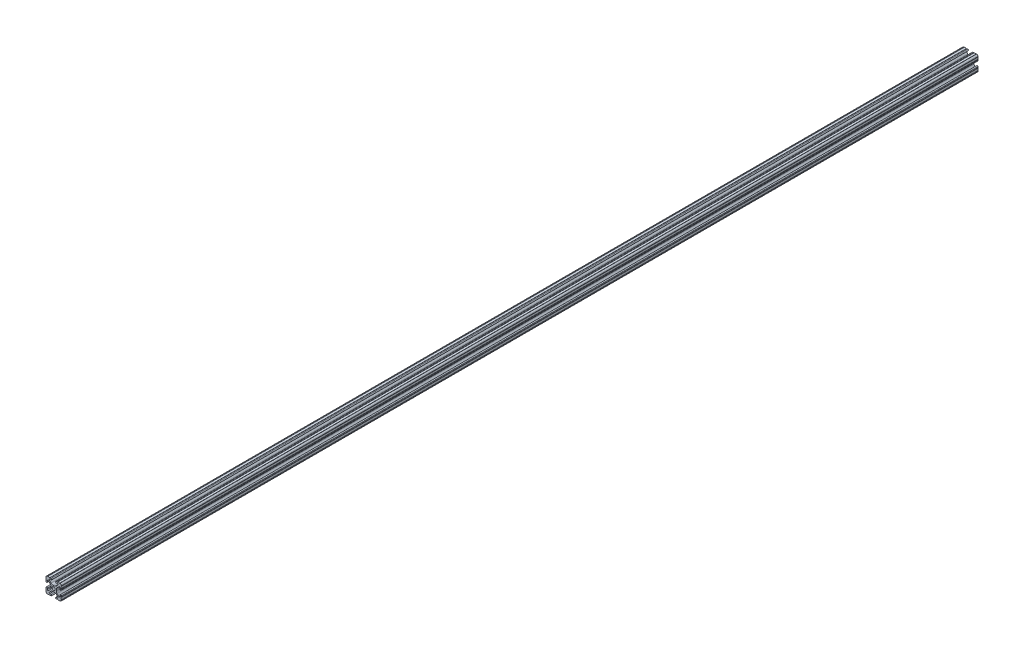
SolidWorks part; units mm, degrees
ref_plane "Front Plane" through (0, 0, 0) normal (0, 0, 1) x (1, 0, 0)
ref_plane "Top Plane" through (0, 0, 0) normal (0, 1, 0) x (1, 0, 0)
ref_plane "Right Plane" through (0, 0, 0) normal (1, 0, 0) x (0, 0, -1)
sketch "Sketch1" plane through (0, 0, 0) normal (0, 0, 1) x (1, 0, 0)
  line L0 (0, 12.7) -> (-12.7814, 12.7) construction
  line L1 (-4.5085, 0) -> (-4.5085, 2.9459)
  line L2 (-6.0437, 12.5461) -> (-10.0976, 12.6876) construction
  line L3 (-11.5616, 12.4229) -> (-4.3159, 12.1699) construction
  line L4 (-6.4364, 10.3486) -> (-6.3592, 12.5571) construction
  line L6 (-2.9459, 4.5085) -> (0, 4.5085)
  line L7 (0, 0) -> (0, 12.7) construction
  line L8 (0, 0) -> (-12.7814, 0) construction
  line L9 (0.7813, 0.7813) -> (-0.7813, -0.7813) construction
  line L10 (-2.9459, 4.5085) -> (-7.1484, 8.711)
  line L11 (-4.5085, 2.9459) -> (-8.711, 7.1484)
  line L13 (0, 0) -> (-12.7814, 12.7814) construction
  line L14 (-10.4131, 12.6987) -> (-4.3048, 12.4853)
  line L15 (-4.3048, 12.4853) -> (-4.382, 10.2769) construction
  line L16 (-4.382, 10.2769) -> (-6.4364, 10.3486)
  line L17 (-12.6987, 10.4131) -> (-12.4853, 4.3048)
  line L18 (-10.2769, 4.382) -> (-10.3486, 6.4364)
  circle A0 centre (0, 0) radius 2.6035
  arc A1 (-4.382, 10.2769) -> (-4.3048, 12.4853) centre (-4.3434, 11.3811) ccw
  arc A2 (-7.1484, 8.711) -> (-6.4364, 10.3486) centre (-6.4698, 9.3896) cw
  arc A3 (-8.711, 7.1484) -> (-10.3486, 6.4364) centre (-9.3896, 6.4698) ccw
  arc A4 (-10.2769, 4.382) -> (-12.4853, 4.3048) centre (-11.3811, 4.3434) cw
  arc A5 (-10.4131, 12.6987) -> (-12.6987, 10.4131) centre (-10.4902, 10.4902) ccw
  arc A6 (-10.4131, 12.6987) -> (-9.7821, 12.6766) centre (-10.0976, 12.6876) ccw
  arc A7 (-6.3592, 12.5571) -> (-5.7282, 12.5351) centre (-6.0437, 12.5461) ccw
  arc A8 (-12.5571, 6.3592) -> (-12.5351, 5.7282) centre (-12.5461, 6.0437) cw
  arc A9 (-12.6987, 10.4131) -> (-12.6766, 9.7821) centre (-12.6876, 10.0976) cw
  dimension "D1" = 5.207
  dimension "D5" = 14.859
  dimension "D9" = 2
  dimension "D2" = 25.4
  dimension "D12" = 0.6314
  dimension "D10" = 2.2098
  dimension "D3" = 9.017
  dimension "D4" = 9.017
  dimension "D6" = 25.4
  dimension "D7" = 6.477
  dimension "D8" = 2.2098
  dimension "D11" = 12.7
sketch "Sketch3" plane through (0, 0, 0) normal (0, 0, 1) x (1, 0, 0)
  line L0 (-2.9459, 4.5085) -> (0, 4.5085) construction
  line L1 (-2.9459, 4.5085) -> (-7.1484, 8.711) construction
  line L2 (-4.382, 10.2769) -> (-6.4364, 10.3486) construction
  line L3 (-10.4131, 12.6987) -> (-4.3048, 12.4853) construction
  line L4 (-4.5085, 0) -> (-4.5085, 2.9459) construction
  line L5 (-4.5085, 2.9459) -> (-8.711, 7.1484) construction
  line L6 (-10.2769, 4.382) -> (-10.3486, 6.4364) construction
  line L7 (-12.6987, 10.4131) -> (-12.4853, 4.3048) construction
  line L8 (-1.1153, 4.5085) -> (1.1153, 4.5085)
  line L9 (-4.2404, 5.803) -> (-7.1484, 8.711)
  line L10 (-4.382, 10.2769) -> (-6.4364, 10.3486)
  line L11 (-9.7821, 12.6766) -> (-6.3592, 12.5571)
  line L12 (-4.5085, -1.1153) -> (-4.5085, 1.1153)
  line L13 (-5.803, 4.2404) -> (-8.711, 7.1484)
  line L14 (-10.2769, 4.382) -> (-10.3486, 6.4364)
  line L15 (-12.6766, 9.7821) -> (-12.5571, 6.3592)
  line L16 (-5.7282, 12.5351) -> (-4.3048, 12.4853)
  line L17 (-12.5351, 5.7282) -> (-12.4853, 4.3048)
  line L18 (0, 0) -> (0, 12.7) construction
  line L19 (0, 0) -> (-12.7814, 0) construction
  line L20 (12.5351, 5.7282) -> (12.4853, 4.3048)
  line L21 (5.7282, 12.5351) -> (4.3048, 12.4853)
  line L22 (12.6766, 9.7821) -> (12.5571, 6.3592)
  line L23 (10.2769, 4.382) -> (10.3486, 6.4364)
  line L24 (5.803, 4.2404) -> (8.711, 7.1484)
  line L25 (4.5085, -1.1153) -> (4.5085, 1.1153)
  line L26 (9.7821, 12.6766) -> (6.3592, 12.5571)
  line L27 (4.382, 10.2769) -> (6.4364, 10.3486)
  line L28 (4.2404, 5.803) -> (7.1484, 8.711)
  line L29 (4.2404, -5.803) -> (7.1484, -8.711)
  line L30 (4.382, -10.2769) -> (6.4364, -10.3486)
  line L31 (9.7821, -12.6766) -> (6.3592, -12.5571)
  line L32 (5.803, -4.2404) -> (8.711, -7.1484)
  line L33 (10.2769, -4.382) -> (10.3486, -6.4364)
  line L34 (12.6766, -9.7821) -> (12.5571, -6.3592)
  line L35 (5.7282, -12.5351) -> (4.3048, -12.4853)
  line L36 (12.5351, -5.7282) -> (12.4853, -4.3048)
  line L37 (-12.5351, -5.7282) -> (-12.4853, -4.3048)
  line L38 (-5.7282, -12.5351) -> (-4.3048, -12.4853)
  line L39 (-12.6766, -9.7821) -> (-12.5571, -6.3592)
  line L40 (-10.2769, -4.382) -> (-10.3486, -6.4364)
  line L41 (-5.803, -4.2404) -> (-8.711, -7.1484)
  line L42 (-9.7821, -12.6766) -> (-6.3592, -12.5571)
  line L43 (-4.382, -10.2769) -> (-6.4364, -10.3486)
  line L44 (-4.2404, -5.803) -> (-7.1484, -8.711)
  line L45 (-1.1153, -4.5085) -> (1.1153, -4.5085)
  arc A0 (-10.4131, 12.6987) -> (-9.7821, 12.6766) centre (-10.0976, 12.6876) ccw construction
  arc A1 (-6.4364, 10.3486) -> (-7.1484, 8.711) centre (-6.4698, 9.3896) ccw construction
  arc A2 (-4.382, 10.2769) -> (-4.3048, 12.4853) centre (-4.3434, 11.3811) ccw construction
  arc A3 (-8.711, 7.1484) -> (-10.3486, 6.4364) centre (-9.3896, 6.4698) ccw construction
  arc A4 (-12.4853, 4.3048) -> (-10.2769, 4.382) centre (-11.3811, 4.3434) ccw construction
  arc A5 (-6.3592, 12.5571) -> (-5.7282, 12.5351) centre (-6.0437, 12.5461) ccw construction
  arc A6 (-10.4131, 12.6987) -> (-12.6987, 10.4131) centre (-10.4902, 10.4902) ccw construction
  arc A7 (-12.6766, 9.7821) -> (-12.6987, 10.4131) centre (-12.6876, 10.0976) ccw construction
  arc A8 (-12.5351, 5.7282) -> (-12.5571, 6.3592) centre (-12.5461, 6.0437) ccw construction
  arc A9 (-10.4131, 12.6987) -> (-9.7821, 12.6766) centre (-10.0976, 12.6876) ccw
  arc A10 (-6.4364, 10.3486) -> (-7.1484, 8.711) centre (-6.4698, 9.3896) ccw
  arc A11 (-4.382, 10.2769) -> (-4.3048, 12.4853) centre (-4.3434, 11.3811) ccw
  arc A12 (-8.711, 7.1484) -> (-10.3486, 6.4364) centre (-9.3896, 6.4698) ccw
  arc A13 (-12.4853, 4.3048) -> (-10.2769, 4.382) centre (-11.3811, 4.3434) ccw
  arc A14 (-6.3592, 12.5571) -> (-5.7282, 12.5351) centre (-6.0437, 12.5461) ccw
  arc A15 (-10.4131, 12.6987) -> (-12.6987, 10.4131) centre (-10.4902, 10.4902) ccw
  arc A16 (-12.6766, 9.7821) -> (-12.6987, 10.4131) centre (-12.6876, 10.0976) ccw
  arc A17 (-12.5351, 5.7282) -> (-12.5571, 6.3592) centre (-12.5461, 6.0437) ccw
  arc A18 (-1.1153, 4.5085) -> (-4.2404, 5.803) centre (-1.1153, 8.9281) cw
  arc A19 (4.5085, 1.1153) -> (5.803, 4.2404) centre (8.9281, 1.1153) cw
  arc A20 (1.1153, 4.5085) -> (4.2404, 5.803) centre (1.1153, 8.9281) ccw
  arc A21 (-4.5085, 1.1153) -> (-5.803, 4.2404) centre (-8.9281, 1.1153) ccw
  arc A22 (12.5351, 5.7282) -> (12.5571, 6.3592) centre (12.5461, 6.0437) cw
  arc A23 (12.6766, 9.7821) -> (12.6987, 10.4131) centre (12.6876, 10.0976) cw
  arc A24 (10.4131, 12.6987) -> (12.6987, 10.4131) centre (10.4902, 10.4902) cw
  arc A25 (6.3592, 12.5571) -> (5.7282, 12.5351) centre (6.0437, 12.5461) cw
  arc A26 (12.4853, 4.3048) -> (10.2769, 4.382) centre (11.3811, 4.3434) cw
  arc A27 (8.711, 7.1484) -> (10.3486, 6.4364) centre (9.3896, 6.4698) cw
  arc A28 (4.382, 10.2769) -> (4.3048, 12.4853) centre (4.3434, 11.3811) cw
  arc A29 (6.4364, 10.3486) -> (7.1484, 8.711) centre (6.4698, 9.3896) cw
  arc A30 (10.4131, 12.6987) -> (9.7821, 12.6766) centre (10.0976, 12.6876) cw
  arc A31 (10.4131, -12.6987) -> (9.7821, -12.6766) centre (10.0976, -12.6876) ccw
  arc A32 (6.4364, -10.3486) -> (7.1484, -8.711) centre (6.4698, -9.3896) ccw
  arc A33 (4.382, -10.2769) -> (4.3048, -12.4853) centre (4.3434, -11.3811) ccw
  arc A34 (8.711, -7.1484) -> (10.3486, -6.4364) centre (9.3896, -6.4698) ccw
  arc A35 (12.4853, -4.3048) -> (10.2769, -4.382) centre (11.3811, -4.3434) ccw
  arc A36 (6.3592, -12.5571) -> (5.7282, -12.5351) centre (6.0437, -12.5461) ccw
  arc A37 (10.4131, -12.6987) -> (12.6987, -10.4131) centre (10.4902, -10.4902) ccw
  arc A38 (12.6766, -9.7821) -> (12.6987, -10.4131) centre (12.6876, -10.0976) ccw
  arc A39 (12.5351, -5.7282) -> (12.5571, -6.3592) centre (12.5461, -6.0437) ccw
  arc A40 (-4.5085, -1.1153) -> (-5.803, -4.2404) centre (-8.9281, -1.1153) cw
  arc A41 (1.1153, -4.5085) -> (4.2404, -5.803) centre (1.1153, -8.9281) cw
  arc A42 (4.5085, -1.1153) -> (5.803, -4.2404) centre (8.9281, -1.1153) ccw
  arc A43 (-1.1153, -4.5085) -> (-4.2404, -5.803) centre (-1.1153, -8.9281) ccw
  arc A44 (-12.5351, -5.7282) -> (-12.5571, -6.3592) centre (-12.5461, -6.0437) cw
  arc A45 (-12.6766, -9.7821) -> (-12.6987, -10.4131) centre (-12.6876, -10.0976) cw
  arc A46 (-10.4131, -12.6987) -> (-12.6987, -10.4131) centre (-10.4902, -10.4902) cw
  arc A47 (-6.3592, -12.5571) -> (-5.7282, -12.5351) centre (-6.0437, -12.5461) cw
  arc A48 (-12.4853, -4.3048) -> (-10.2769, -4.382) centre (-11.3811, -4.3434) cw
  arc A49 (-8.711, -7.1484) -> (-10.3486, -6.4364) centre (-9.3896, -6.4698) cw
  arc A50 (-4.382, -10.2769) -> (-4.3048, -12.4853) centre (-4.3434, -11.3811) cw
  arc A51 (-6.4364, -10.3486) -> (-7.1484, -8.711) centre (-6.4698, -9.3896) cw
  arc A52 (-10.4131, -12.6987) -> (-9.7821, -12.6766) centre (-10.0976, -12.6876) cw
  circle A53 centre (0, 0) radius 2.6035 construction
  circle A54 centre (0, 0) radius 2.6035
  point P135 (4.5085, 0)
  dimension "D2" = 4.4196
extrude "Extrude1" add sketch "Sketch3" along normal mid plane 1524
equation "\"D10@Sketch1\" = \"D8@Sketch1\""
equation "\"D11@Sketch1\" = \"D6@Sketch1\"/2"
equation "\"D12@Sketch1\" = \"D8@Sketch1\"/3.5"
equation "\"D2@Sketch3\" = \"D8@Sketch1\"*2"
